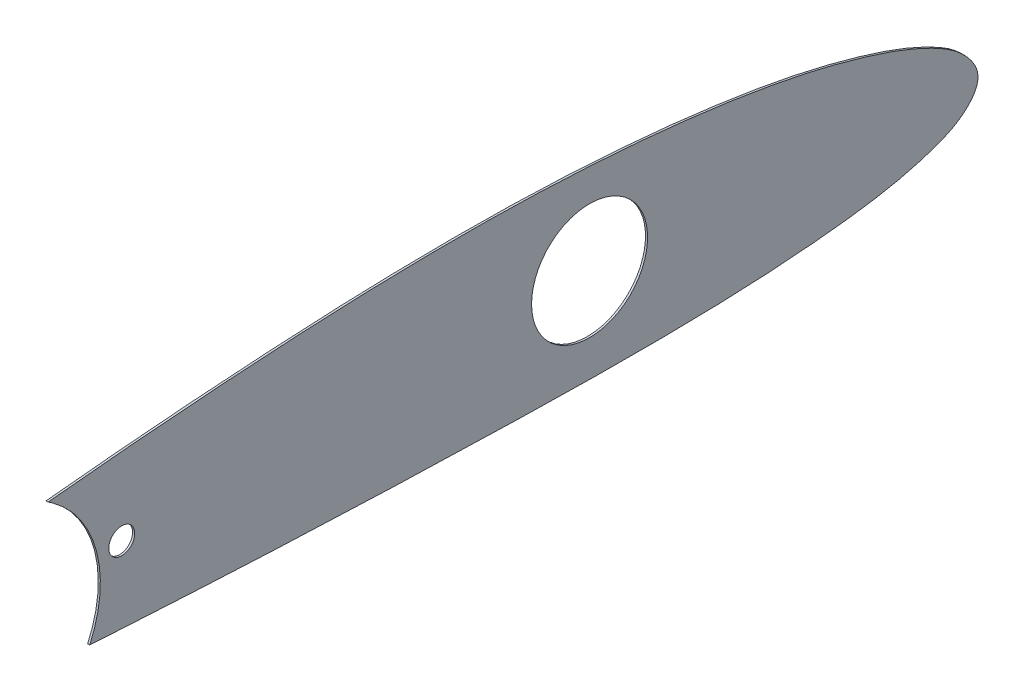
SolidWorks part; units mm, degrees
material "ABS"
ref_plane "Front Plane" through (0, 0, 0) normal (0, 0, 1) x (1, 0, 0)
ref_plane "Top Plane" through (0, 0, 0) normal (0, 1, 0) x (1, 0, 0)
ref_plane "Right Plane" through (0, 0, 0) normal (1, 0, 0) x (0, 0, -1)
body saved out of another part "Stock-P01-30-02-11_260807_NACA2412_3Dmodel_test_RH-1" rebuild error yes
sketch "Sketch3" plane through (899, 0, 0) normal (-1, 0, 0) x (0, 0, 1)
  line L0 (74.9825, 5.5405) -> (165.3194, 5.5405) construction
  line L1 (165.3194, 5.5405) -> (165.3194, 31.0922) construction
  line L2 (166.5194, 9.9812) -> (166.5194, 20.3782)
  line L3 (166.5194, 1.0998) -> (166.5194, -9.0912)
  line L4 (164.1194, 1.0998) -> (164.1194, -9.2318)
  line L5 (164.1194, 20.5898) -> (164.1194, 9.9812)
  circle A0 centre (74.9825, 5.5405) radius 10.1 construction
  circle A1 centre (165.3194, 5.5405) radius 2.5
  arc A2 (166.5194, 9.9812) -> (166.5194, 1.0998) centre (165.3194, 5.5405) ccw
  arc A3 (164.1194, 1.0998) -> (164.1194, 9.9812) centre (165.3194, 5.5405) ccw
  circle A4 centre (74.9825, 5.5405) radius 10.1 construction
  circle A5 centre (74.9825, 5.5405) radius 11.2 construction
  circle A6 centre (74.9825, 5.5405) radius 11.2 construction
  arc A9 (178.5261, 18.427) -> (171.5103, -8.7945) centre (191.6081, 0.5405) ccw construction
  spline S0 degree 3 poles (166.5194, -9.0912) (165.7194, -9.1378) (164.9194, -9.1847) (164.1194, -9.2318) knots 0.777434 0.777434 0.777434 0.777434 0.781364 0.781364 0.781364 0.781364
  spline S1 degree 3 poles (164.1194, 20.5898) (164.9193, 20.5183) (165.7193, 20.4478) (166.5194, 20.3782) knots 0.220717 0.220717 0.220717 0.220717 0.224654 0.224654 0.224654 0.224654
  spline S2 degree 3 poles (179.5417, 19.1273) (169.7083, 20.1389) (149.8799, 21.8677) (120.0263, 23.6351) (94.9907, 23.9358) (74.9819, 23.1075) (59.963, 21.8937) (44.9251, 19.9716) (32.4099, 17.6048) (22.4325, 14.927) (14.8683, 12.4925) (8.4595, 9.6559) (2.9313, 6.2169) (-1.8895, 0.2696) (3.118, -4.9579) (8.5428, -7.3422) (14.9234, -9.1532) (22.4628, -10.4518) (32.4801, -11.56) (44.9841, -12.4129) (59.9982, -12.7549) (75.0016, -12.7072) (95.0035, -12.2657) (120.0081, -11.4712) (147.1778, -10.2191) (164.3414, -9.2244) (171.5102, -8.7945) knots 0.210464 0.210464 0.210464 0.210464 0.258935 0.308047 0.357083 0.381622 0.406221 0.430945 0.455929 0.46862 0.481537 0.49501 0.502394 0.514589 0.524739 0.531581 0.544366 0.556821 0.569162 0.593739 0.618265 0.642782 0.667305 0.716364 0.765451 0.800666 0.800666 0.800666 0.800666 construction
  dimension "D2" = 5
  dimension "D3" = 4.6
  dimension "D4" = 20.2
  dimension "D1" = 1.2
extrude "Boss-Extrude2" add sketch "Sketch3" against normal up to surface (8.3627 mm away) rebuild error yes
sketch "Sketch4" plane through (899, 0, 0) normal (-1, 0, 0) x (0, 0, 1)
  circle A0 centre (165.3194, 5.5405) radius 2.5 construction
  circle A1 centre (165.3194, 5.5405) radius 2.5
extrude "Cut-Extrude1" cut sketch "Sketch4" against normal up to surface (45.2241 mm away) rebuild error yes
sketch "Sketch1" plane through (899, 0, 0) normal (-1, 0, 0) x (0, 0, 1)
  line L1 (178.5261, 18.427) -> (178.5264, 18.427)
  line L2 (178.5261, 18.427) -> (178.5264, 18.427)
  line L4 (164.1209, -9.2317) -> (166.5178, -9.0913)
  line L5 (164.1209, -9.2317) -> (166.5178, -9.0913)
  arc A0 (179.5417, 19.1273) -> (178.5264, 18.427) centre (191.6474, 0.4894) ccw
  arc A1 (178.5261, 18.427) -> (171.5102, -8.7945) centre (191.6081, 0.5405) ccw
  arc A2 (179.5417, 19.1273) -> (178.5264, 18.427) centre (191.6474, 0.4894) ccw
  arc A3 (178.5261, 18.427) -> (171.5102, -8.7945) centre (191.6081, 0.5405) ccw
  circle A4 centre (74.9825, 5.5405) radius 11.2 construction
  circle A5 centre (74.9825, 5.5405) radius 11.2
  circle A6 centre (165.3194, 5.5405) radius 2.5 construction
  circle A7 centre (165.3194, 5.5405) radius 2.5
  spline S3 degree 3 poles (-918.2708, -12564.1988) (1722.8439, -1044.5189) (962.1388, -26.221) (120.0263, 23.6351) (94.9907, 23.9358) (74.9819, 23.1075) (59.963, 21.8937) (44.9251, 19.9716) (32.4099, 17.6048) (22.4325, 14.927) (14.8683, 12.4925) (8.4595, 9.6559) (2.9313, 6.2169) (-1.8895, 0.2696) (3.118, -4.9579) (8.5428, -7.3422) (14.9234, -9.1532) (22.4628, -10.4518) (32.4801, -11.56) (44.9841, -12.4129) (59.9982, -12.7549) (75.0016, -12.7072) (95.0035, -12.2657) (120.0081, -11.4712) (756.5027, 17.8613) (1368.1212, 317.1869) (2657.1082, -12524.0681) knots -3.766648 -3.766648 -3.766648 -3.766648 0.271034 0.320146 0.369182 0.393721 0.41832 0.443044 0.468028 0.480719 0.493635 0.507108 0.514493 0.526688 0.536838 0.54368 0.556464 0.56892 0.581261 0.605838 0.630364 0.654881 0.679403 0.728463 0.777549 3.803614 3.803614 3.803614 3.803614 only from (179.5417, 19.1273) to (164.1209, -9.2317)
  spline S4 degree 3 poles (179.5417, 19.1273) (169.7083, 20.1389) (149.8799, 21.8677) (120.0263, 23.6351) (94.9907, 23.9358) (74.9819, 23.1075) (59.963, 21.8937) (44.9251, 19.9716) (32.4099, 17.6048) (22.4325, 14.927) (14.8683, 12.4925) (8.4595, 9.6559) (2.9313, 6.2169) (-1.8895, 0.2696) (3.118, -4.9579) (8.5428, -7.3422) (14.9234, -9.1532) (22.4628, -10.4518) (32.4801, -11.56) (44.9841, -12.4129) (59.9982, -12.7549) (75.0016, -12.7072) (95.0035, -12.2657) (120.0081, -11.4712) (144.7129, -10.3327) (159.4146, -9.5057) (164.1209, -9.2317) knots 0.222563 0.222563 0.222563 0.222563 0.271034 0.320146 0.369182 0.393721 0.41832 0.443044 0.468028 0.480719 0.493635 0.507108 0.514493 0.526688 0.536838 0.54368 0.556464 0.56892 0.581261 0.605838 0.630364 0.654881 0.679403 0.728463 0.777549 0.800666 0.800666 0.800666 0.800666
  spline S6 degree 3 poles (-2292.0572, 12539.9479) (244.3827, -12695.64) (128.4473, 12671.3364) (2657.7609, -12530.5706) knots -2.726825 -2.726825 -2.726825 -2.726825 3.209999 3.209999 3.209999 3.209999 only from (166.5178, -9.0913) to (171.5102, -8.7945)
  spline S7 degree 3 poles (166.5178, -9.0913) (168.182, -8.9933) (169.8461, -8.8943) (171.5102, -8.7945) knots 0.210464 0.210464 0.210464 0.210464 0.218639 0.218639 0.218639 0.218639
  dimension "D1" = 0
extrude "Boss-Extrude1" add sketch "Sketch1" against normal blind 0.4
sketch "Sketch5" plane through (1117, 0, 0) normal (1, 0, 0) x (0, 0, -1)
  line L0 (-164.1194, 1.0998) -> (-164.1194, -9.2318) construction
  line L1 (-166.5194, 1.0998) -> (-166.5194, -9.0912) construction
  line L2 (-164.1194, 20.5898) -> (-164.1194, 9.9812) construction
  line L3 (-166.5194, 9.9812) -> (-166.5194, 20.3782) construction
  line L4 (-164.1194, 1.0998) -> (-164.1194, -9.2318)
  line L5 (-166.5194, 1.0998) -> (-166.5194, -9.0912)
  line L6 (-164.1194, 20.5898) -> (-164.1194, 9.9812)
  line L7 (-166.5194, 9.9812) -> (-166.5194, 20.3782)
  arc A0 (-164.1194, -9.2318) -> (-166.5194, -9.0912) centre (-386.3474, -3783.4872) ccw construction
  circle A1 centre (-165.3194, 5.5405) radius 2.5 construction
  arc A2 (-164.1194, 9.9812) -> (-164.1194, 1.0998) centre (-165.3194, 5.5405) ccw construction
  arc A3 (-166.5194, 1.0998) -> (-166.5194, 9.9812) centre (-165.3194, 5.5405) ccw construction
  arc A4 (-166.5194, 20.3782) -> (-164.1194, 20.5898) centre (-253.8097, 1024.2016) ccw construction
  arc A5 (-164.1194, -9.2318) -> (-166.5194, -9.0912) centre (-386.3474, -3783.4872) ccw
  circle A6 centre (-165.3194, 5.5405) radius 2.5
  arc A7 (-164.1194, 9.9812) -> (-164.1194, 1.0998) centre (-165.3194, 5.5405) ccw
  arc A8 (-166.5194, 1.0998) -> (-166.5194, 9.9812) centre (-165.3194, 5.5405) ccw
  arc A9 (-166.5194, 20.3782) -> (-164.1194, 20.5898) centre (-253.8097, 1024.2016) ccw
extrude "Boss-Extrude3" add sketch "Sketch5" against normal up to surface (30.9246 mm away) rebuild error yes
